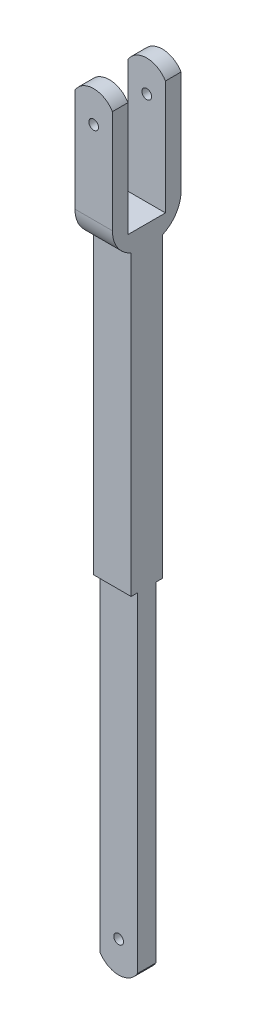
SolidWorks part; units mm, degrees
ref_plane "Front Plane" through (0, 0, 0) normal (0, 0, 1) x (1, 0, 0)
ref_plane "Top Plane" through (0, 0, 0) normal (0, 1, 0) x (1, 0, 0)
ref_plane "Right Plane" through (0, 0, 0) normal (1, 0, 0) x (0, 0, -1)
sketch "Esquisse1" plane through (0, 0, 0) normal (0, 0, 1) x (1, 0, 0)
  line L2 (-6.8285, -151.713) -> (-6.8285, 91.4981)
  line L4 (5.1715, -151.713) -> (5.1715, 91.4981)
  arc A0 (5.1715, 91.4981) -> (-6.8285, 91.4981) centre (-0.8285, 87.8925) ccw
  arc A1 (-6.8285, -151.713) -> (5.1715, -151.713) centre (-0.8285, -148.1075) ccw
  point P0 (0, 0)
  point P1 (-0.8285, -155.1075)
  point P3 (-0.8285, 94.8925)
  dimension "D3" = 14
  dimension "D4" = 14
  dimension "D1" = 250
  dimension "D2" = 12
extrude "Boss.-Extru.1" add sketch "Esquisse1" along normal blind 11 and the other way blind 11
ref_plane "Plane1" through (0, 94.8925, 0) normal (0, 1, 0) x (1, 0, 0)
sketch "Esquisse3" plane through (0, 94.8925, 0) normal (0, 1, 0) x (1, 0, 0)
  line L7 (-7, 0) -> (49993, 0) construction
  line L13 (-8.0887, -6) -> (8.4927, -6)
  line L14 (-8.0887, -6) -> (-8.0887, 6)
  line L15 (-8.0887, 6) -> (8.4927, 6)
  line L17 (8.4927, -6) -> (8.4927, 6)
  line L18 (-8.0887, -6) -> (8.4927, 6) construction
  line L19 (-8.0887, 6) -> (8.4927, -6) construction
  line L20 (5.1715, 11) -> (-6.8285, 11) construction
  line L21 (-6.8285, -11) -> (5.1715, -11) construction
  point P5 (0.202, 0)
  dimension "D1" = 5
  dimension "D2" = 5
extrude "Enlèv. mat.-Extru.2" cut sketch "Esquisse3" against normal blind 40
sketch "Sketch1" plane through (0, 0, 11) normal (0, 0, 1) x (1, 0, 0)
  line L1 (-0.8285, 90.5285) -> (-0.8285, -49909.4715) construction
  line L2 (-6.8285, 91.4981) -> (-6.8285, -151.713) construction
  line L3 (5.1715, -151.713) -> (5.1715, 91.4981) construction
  circle A0 centre (-0.8285, 84.8904) radius 1.55
  circle A1 centre (-0.8285, -145.1075) radius 1.55
  arc A6 (5.1715, 91.4981) -> (-6.8285, 91.4981) centre (-0.8285, 87.8925) ccw construction
  arc A7 (-6.8285, -151.713) -> (5.1715, -151.713) centre (-0.8285, -148.1075) ccw construction
  point P11 (-0.8285, 94.8925)
  point P16 (-0.8285, -155.1075)
  dimension "D1" = 3.1
  dimension "D2" = 10.0021
  dimension "D3" = 3.1
  dimension "D4" = 10
extrude "Cut-Extrude1" cut sketch "Sketch1" against normal up to surface (22 mm away) up to face at (-0.8285, -30.1075, -11)
sketch "Sketch4" plane through (0, 0, 11) normal (0, 0, 1) x (1, 0, 0)
  line L0 (-6.8285, 49.2783) -> (-6.8285, -151.713)
  line L1 (-6.8285, 91.4981) -> (-6.8285, -151.713) construction
  line L2 (-6.8285, 49.2783) -> (5.1715, 49.2783)
  line L3 (5.1715, -151.713) -> (5.1715, 91.4981) construction
  line L4 (5.1715, 49.2783) -> (5.1715, -151.713)
  arc A0 (-6.8285, -151.713) -> (5.1715, -151.713) centre (-0.8285, -151.713) ccw
  arc A1 (-6.8285, -151.713) -> (5.1715, -151.713) centre (-0.8285, -148.1075) ccw construction
extrude "Cut-Extrude2" cut sketch "Sketch4" against normal blind 6
mirror "Mirror1" about plane through (0, 0, 0) normal (0, 0, 1) of "Cut-Extrude2"
fillet "Fillet1" radius 10 2 edges at (-0.8285, 49.2783, -11) (-0.8285, 49.2783, 11)
sketch "Sketch5" plane through (0, 0, -5) normal (0, 0, -1) x (-1, 0, 0)
  line L0 (-5.1715, -151.713) -> (-5.1715, -46.0541)
  line L1 (-5.1715, -151.713) -> (-5.1715, 49.2783) construction
  line L2 (6.8285, -151.713) -> (6.8285, -46.0541)
  line L3 (6.8285, 49.2783) -> (6.8285, -151.713) construction
  line L4 (-5.1715, -46.0541) -> (6.8285, -46.0541)
  arc A0 (-5.1715, -151.713) -> (6.8285, -151.713) centre (0.8285, -148.1075) ccw
extrude "Cut-Extrude3" cut sketch "Sketch5" against normal blind 2
mirror "Mirror2" about plane through (0, 0, 0) normal (0, 0, 1) of "Cut-Extrude3"
equation "\"ScrewSize\"= 3.1mm"
